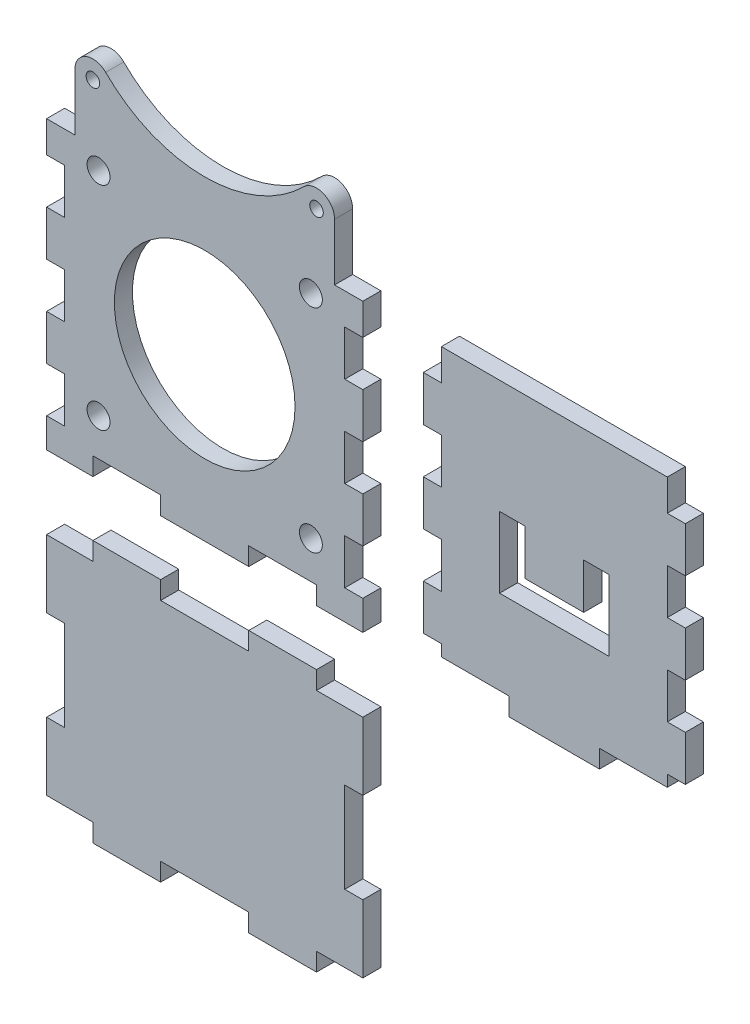
SolidWorks part; units mm, degrees
ref_plane "Front Plane" through (0, 0, 0) normal (0, 0, 1) x (1, 0, 0)
ref_plane "Top Plane" through (0, 0, 0) normal (0, 1, 0) x (1, 0, 0)
ref_plane "Right Plane" through (0, 0, 0) normal (1, 0, 0) x (0, 0, -1)
sketch "Sketch1" plane through (0, 0, 0) normal (0, 0, 1) x (1, 0, 0)
  line L0 (-24.7487, -24.7487) -> (0, 0) construction
  line L1 (0, 0) -> (24.7487, -24.7487) construction
  line L2 (0, -37.3307) -> (0, -35) construction
  line L3 (-35, -100.8307) -> (35, -100.8307)
  line L4 (-28.7487, -24.7487) -> (-28.7487, -37.3307)
  line L5 (-35, -64.2788) -> (-31, -64.2788)
  line L6 (28.7487, -24.7487) -> (28.7487, -37.3307)
  line L7 (-35, -100.8307) -> (-35, -37.3307)
  line L8 (-35, -37.3307) -> (-28.7487, -37.3307)
  line L9 (35, -100.8307) -> (35, -37.3307)
  line L10 (-23.5, -41.5497) -> (23.5, -41.5497) construction
  line L11 (-35, -44.2788) -> (-31, -44.2788)
  line L12 (-35, -44.2788) -> (-35, -54.2788)
  line L13 (-35, -54.2788) -> (-31, -54.2788)
  line L14 (-31, -44.2788) -> (-31, -54.2788)
  line L15 (23.5, -41.5497) -> (23.5, -88.5497) construction
  line L16 (23.5, -88.5497) -> (-23.5, -88.5497) construction
  line L17 (-23.5, -88.5497) -> (-23.5, -41.5497) construction
  line L18 (0, -37.3307) -> (0, -41.5497) construction
  line L19 (28.7487, -37.3307) -> (35, -37.3307)
  line L20 (-35, -64.2788) -> (-35, -74.2788)
  line L21 (-31, -64.2788) -> (-31, -74.2788)
  line L22 (-35, -74.2788) -> (-31, -74.2788)
  line L23 (-35, -84.2788) -> (-31, -84.2788)
  line L24 (-35, -84.2788) -> (-35, -94.2788)
  line L25 (-31, -84.2788) -> (-31, -94.2788)
  line L26 (-35, -94.2788) -> (-31, -94.2788)
  line L27 (35, -64.2788) -> (31, -64.2788)
  line L28 (35, -44.2788) -> (31, -44.2788)
  line L29 (35, -44.2788) -> (35, -54.2788)
  line L30 (35, -54.2788) -> (31, -54.2788)
  line L31 (31, -44.2788) -> (31, -54.2788)
  line L32 (31, -64.2788) -> (31, -74.2788)
  line L33 (35, -74.2788) -> (31, -74.2788)
  line L34 (35, -84.2788) -> (31, -84.2788)
  line L35 (31, -84.2788) -> (31, -94.2788)
  line L36 (35, -94.2788) -> (31, -94.2788)
  line L37 (-9.7487, -96.8307) -> (9.7487, -96.8307) construction
  line L38 (-24.7487, -100.8307) -> (-9.7487, -100.8307)
  line L39 (-24.7487, -100.8307) -> (-24.7487, -96.8307)
  line L40 (-24.7487, -96.8307) -> (-9.7487, -96.8307)
  line L41 (-9.7487, -100.8307) -> (-9.7487, -96.8307)
  line L42 (9.7487, -100.8307) -> (24.7487, -100.8307)
  line L43 (9.7487, -100.8307) -> (9.7487, -96.8307)
  line L44 (9.7487, -96.8307) -> (24.7487, -96.8307)
  line L45 (24.7487, -100.8307) -> (24.7487, -96.8307)
  line L46 (-24.7487, -96.8307) -> (-35, -96.8307) construction
  line L47 (0, -88.5497) -> (0, -96.8307) construction
  line L48 (24.7487, -96.8307) -> (35, -96.8307) construction
  line L49 (87.3929, -96.8307) -> (102.3929, -96.8307)
  line L50 (52.3929, -37.3307) -> (102.3929, -37.3307)
  line L51 (52.3929, -37.3307) -> (52.3929, -44.2788)
  line L52 (52.3929, -96.8307) -> (67.3929, -96.8307)
  line L53 (102.3929, -37.3307) -> (102.3929, -44.2788)
  line L54 (52.3929, -44.2788) -> (48.3929, -44.2788)
  line L55 (102.3929, -54.2788) -> (102.3929, -64.2788)
  line L56 (52.3929, -54.2788) -> (48.3929, -54.2788)
  line L57 (48.3929, -44.2788) -> (48.3929, -54.2788)
  line L58 (52.3929, -64.2788) -> (48.3929, -64.2788)
  line L59 (52.3929, -94.2788) -> (52.3929, -96.8307)
  line L60 (52.3929, -74.2788) -> (48.3929, -74.2788)
  line L61 (48.3929, -64.2788) -> (48.3929, -74.2788)
  line L62 (52.3929, -84.2788) -> (48.3929, -84.2788)
  line L63 (102.3929, -94.2788) -> (102.3929, -96.8307)
  line L64 (52.3929, -94.2788) -> (48.3929, -94.2788)
  line L65 (48.3929, -84.2788) -> (48.3929, -94.2788)
  line L66 (106.3929, -44.2788) -> (102.3929, -44.2788)
  line L67 (106.3929, -44.2788) -> (106.3929, -54.2788)
  line L68 (106.3929, -54.2788) -> (102.3929, -54.2788)
  line L69 (102.3929, -74.2788) -> (102.3929, -84.2788)
  line L70 (102.3929, -64.2788) -> (106.3929, -64.2788)
  line L71 (52.3929, -74.2788) -> (52.3929, -84.2788)
  line L72 (102.3929, -74.2788) -> (106.3929, -74.2788)
  line L73 (106.3929, -64.2788) -> (106.3929, -74.2788)
  line L74 (102.3929, -84.2788) -> (106.3929, -84.2788)
  line L75 (31, -132.0703) -> (31, -117.0703) construction
  line L76 (102.3929, -94.2788) -> (106.3929, -94.2788)
  line L77 (106.3929, -84.2788) -> (106.3929, -94.2788)
  line L78 (52.3929, -54.2788) -> (52.3929, -64.2788)
  line L79 (67.3929, -96.8307) -> (67.3929, -100.8307)
  line L80 (67.3929, -100.8307) -> (87.3929, -100.8307)
  line L81 (87.3929, -96.8307) -> (87.3929, -100.8307)
  line L82 (-35, -117.0703) -> (35, -117.0703)
  line L83 (-35, -117.0703) -> (-35, -167.0703)
  line L84 (-35, -167.0703) -> (35, -167.0703)
  line L85 (35, -117.0703) -> (35, -167.0703)
  line L86 (-24.7487, -117.0703) -> (-9.7487, -117.0703)
  line L87 (-24.7487, -117.0703) -> (-24.7487, -113.0703)
  line L88 (-24.7487, -113.0703) -> (-9.7487, -113.0703)
  line L89 (-9.7487, -117.0703) -> (-9.7487, -113.0703)
  line L90 (9.7487, -117.0703) -> (24.7487, -117.0703)
  line L91 (9.7487, -117.0703) -> (9.7487, -113.0703)
  line L92 (9.7487, -113.0703) -> (24.7487, -113.0703)
  line L93 (24.7487, -117.0703) -> (24.7487, -113.0703)
  line L94 (-24.7487, -167.0703) -> (-9.7487, -167.0703)
  line L95 (-24.7487, -167.0703) -> (-24.7487, -171.0703)
  line L96 (-24.7487, -171.0703) -> (-9.7487, -171.0703)
  line L97 (-9.7487, -167.0703) -> (-9.7487, -171.0703)
  line L98 (9.7487, -167.0703) -> (24.7487, -167.0703)
  line L99 (9.7487, -167.0703) -> (9.7487, -171.0703)
  line L100 (9.7487, -171.0703) -> (24.7487, -171.0703)
  line L101 (24.7487, -167.0703) -> (24.7487, -171.0703)
  line L102 (35, -132.0703) -> (31, -132.0703)
  line L103 (35, -132.0703) -> (35, -152.0703)
  line L104 (35, -152.0703) -> (31, -152.0703)
  line L105 (31, -132.0703) -> (31, -152.0703)
  line L106 (-35, -132.0703) -> (-31, -132.0703)
  line L107 (-35, -132.0703) -> (-35, -152.0703)
  line L108 (-35, -152.0703) -> (-31, -152.0703)
  line L109 (-31, -132.0703) -> (-31, -152.0703)
  line L110 (31, -152.0703) -> (31, -167.0703) construction
  line L111 (65.2727, -78.1598) -> (52.3929, -78.1598) construction
  line L112 (65.2727, -62.4817) -> (70.8931, -62.4817)
  line L113 (65.2727, -62.4817) -> (65.2727, -78.1598)
  line L114 (65.2727, -78.1598) -> (70.8931, -78.1598)
  line L115 (70.8931, -62.4817) -> (70.8931, -78.1598)
  line L116 (83.8928, -62.4817) -> (89.5132, -62.4817)
  line L117 (83.8928, -62.4817) -> (83.8928, -78.1598)
  line L118 (83.8928, -78.1598) -> (89.5132, -78.1598)
  line L119 (89.5132, -62.4817) -> (89.5132, -78.1598)
  line L120 (70.8931, -78.1598) -> (83.8928, -78.1598)
  line L121 (70.8931, -78.1598) -> (70.8931, -72.5394)
  line L122 (70.8931, -72.5394) -> (83.8928, -72.5394)
  line L123 (83.8928, -78.1598) -> (83.8928, -72.5394)
  line L124 (89.5132, -78.1598) -> (102.3929, -78.1598) construction
  line L125 (77.3929, -72.5394) -> (77.3929, -78.1598) construction
  line L126 (-23.5, -41.5497) -> (23.5, -88.5497) construction
  circle A0 centre (0, 0) radius 30 construction
  circle A1 centre (-24.7487, -24.7487) radius 5 construction
  circle A2 centre (24.7487, -24.7487) radius 5 construction
  circle A3 centre (-24.7487, -24.7487) radius 1.5
  circle A4 centre (24.7487, -24.7487) radius 1.5
  arc A5 (-24.7487, -24.7487) -> (24.7487, -24.7487) centre (0, 0) ccw construction
  circle A6 centre (23.5, -41.5497) radius 2.54
  arc A7 (-21.9203, -21.9203) -> (21.9203, -21.9203) centre (0, 0) ccw
  arc A8 (-21.9203, -21.9203) -> (-28.7487, -24.7487) centre (-24.7487, -24.7487) ccw
  arc A9 (28.7487, -24.7487) -> (21.9203, -21.9203) centre (24.7487, -24.7487) ccw
  circle A10 centre (23.5, -88.5497) radius 2.54
  circle A11 centre (-23.5, -88.5497) radius 2.54
  circle A12 centre (-23.5, -41.5497) radius 2.54
  circle A13 centre (0, -65.0497) radius 20
  point P10 (0, -35)
  dimension "D1" = 3
  dimension "D2" = 3
extrude "Boss-Extrude1" add sketch "Sketch1" along normal blind 4 contours L6 A10 A8 A9 L4 L8 L7 L11 L14 L13 L5 L21 L22 L23 L25 L26 L3 L39 L40 L41 L43 L44 L45 L19 L36 L35 L34 L33 L32 L27 L30 L31 L28 L29 L126 A12 A11 A4 | A0 L89 L88 L87 L83 L84 L106 L109 L108 L103 L86 L95 L96 L97 L94 L99 L100 L101 L98 L107 L104 L105 L102 L85 L90 L93 L92 L91 | L81 L49 L64 L77 L78 L74 L71 L76 L73 L70 L56 L69 L67 L66 L55 L50 L53 L54 L59 L57 L82 L58 L63 L61 L72 L62 L68 L65 L60 L52 L79 L80 L115 L122 L117 L116 L119 L118 L120 L114 L113 L112 | L82 L93 L92 L91 | L101 L84 L99 L100 | L97 L84 L95 L96 | L88 L89 L86 L87 region at (-33.9364, -97.5548, 0) region at (77.3929, -67.702, 0) region at (0, -142.0703, 0) region at (17.2487, -115.0703, 0) region at (-17.2487, -169.0703, 0) region at (17.2487, -169.0703, 0)
